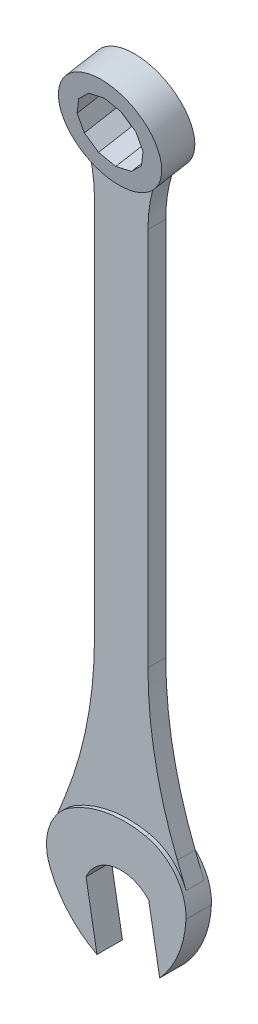
SolidWorks part; units mm, degrees
ref_plane "Front Plane" through (0, 0, 0) normal (1, 0, 0) x (0, 1, 0)
ref_plane "Top Plane" through (0, 0, 0) normal (0, 0, 1) x (0, 1, 0)
ref_plane "Right Plane" through (0, 0, 0) normal (0, 1, 0) x (-1, 0, 0)
sketch "head + handle sketch" plane through (0, 0, 0) normal (0, 0, 1) x (0, 1, 0)
  line L0 (-1.3783, 7.8169) -> (-16.8371, 5.0911)
  line L1 (1.3783, -7.8169) -> (-14.0804, -10.5427)
  line L2 (-1.3783, 7.8169) -> (1.3783, -7.8169) construction
  line L3 (-5.0941, -0.8982) -> (0, 0) construction
  line L4 (-5.0941, -0.8982) -> (-10.0056, -1.7643) construction
  line L5 (0, 0) -> (-15.9394, 0) construction
  line L6 (-14.0804, -10.5427) -> (-16.8371, 5.0911) construction
  line L7 (-4.1052, 16.7007) -> (1.8543, -17.0976) construction
  line L8 (14.8371, -7.0558) -> (11.5291, 11.7048) construction
  line L9 (-14.3514, 15.2013) -> (9.6201, 19.4282) construction
  line L10 (-9.4772, -19.403) -> (13.9076, -15.2796) construction
  line L11 (50.3209, 6.6675) -> (145.1557, 6.6675)
  line L12 (164.2057, 12.065) -> (164.2057, -12.065)
  line L13 (0, 0) -> (164.2057, 0) construction
  line L14 (145.1557, -6.6675) -> (50.5079, -6.6675)
  line L15 (12.7689, 13.862) -> (5.4557, 16.771)
  line L16 (12.621, -13.9958) -> (7.1516, -16.194)
  line L17 (165.1, 0) -> (165.1, 14.0481)
  arc A0 (-1.3783, 7.8169) -> (1.3783, -7.8169) centre (-5.0941, -0.8982) cw
  arc A1 (-16.8371, 5.0911) -> (-4.1052, 16.7007) centre (5.6286, -6.7602) cw
  arc A2 (-4.1052, 16.7007) -> (11.5291, 11.7048) centre (0.7617, 4.9703) cw
  arc A3 (11.5291, 11.7048) -> (14.8371, -7.0558) centre (-10.0056, -1.7643) cw
  arc A4 (14.8371, -7.0558) -> (1.8543, -17.0976) centre (2.4157, -4.41) cw
  arc A5 (1.8543, -17.0976) -> (-14.0804, -10.5427) centre (2.9771, 8.2776) cw
  arc A6 (50.3209, 6.6675) -> (12.7689, 13.862) centre (50.3209, 108.2675) cw
  arc A7 (145.1557, 6.6675) -> (164.2057, 12.065) centre (145.1557, 42.9839) ccw
  arc A8 (145.1557, -6.6675) -> (164.2057, -12.065) centre (145.1557, -42.9839) cw
  arc A9 (50.5079, -6.6675) -> (12.621, -13.9958) centre (50.5079, -108.2675) ccw
  point P29 (30.8557, 6.6675)
  point P37 (165.1, 0)
  point P41 (30.8557, -6.6675)
  dimension "D2" = 9.4742
  dimension "D3" = 25.4
  dimension "D4" = 12.7
  dimension "D5" = 25.4
  dimension "D7" = 10
  dimension "D9" = 34.925
  dimension "D11" = 101.6
  dimension "D16" = 101.6
  dimension "D1" = 15.875
  dimension "D6" = 10.16
  dimension "D8" = 15.6972
  dimension "D10" = 25.4
  dimension "D12" = 19.05
  dimension "D13" = 24.13
  dimension "D14" = 6.6675
  dimension "D15" = 158.75
  dimension "D17" = 165.1
extrude "head extrude" add sketch "head + handle sketch" along normal blind 3.175 and the other way blind 3.175 contours A5 A4 A3 A2 A1 L0 A0 L1 region at (-6.921, -9.19, 0)
extrude "handle extrude" add sketch "Sketch2<3>" along normal blind 2.2225 and the other way blind 2.2225 contours L14 A8 L12 A7 L11 A2 A3 A4 region at (-0.0501, 86.1411, 0)
sketch "Sketch2<3>" plane through (0, 0, 0) normal (0, 0, 1) x (0, 1, 0) same geometry as "head + handle sketch"
ref_plane "rear circle plane" through (0, 4.9784, -28.2338) normal (0, 0.1736, -0.9848) x (-1, 0, 0)
sketch "rear circle sketch" plane through (0, 4.9784, -28.2338) normal (0, 0.1736, -0.9848) x (-1, 0, 0)
  line L0 (-7.1166, 158.483) -> (-4.1088, 155.4752)
  line L1 (7.1166, 166.7005) -> (4.1088, 169.7083)
  line L2 (4.1088, 169.7083) -> (0, 170.8093)
  line L3 (0, 170.8093) -> (-4.1088, 169.7083)
  line L4 (-4.1088, 169.7083) -> (-7.1166, 166.7005)
  line L5 (-7.1166, 166.7005) -> (-8.2175, 162.5918)
  line L6 (-8.2175, 162.5918) -> (-7.1166, 158.483)
  line L7 (-4.1088, 155.4752) -> (0, 154.3743)
  line L8 (0, 154.3743) -> (4.1088, 155.4752)
  line L9 (4.1088, 155.4752) -> (7.1166, 158.483)
  line L10 (7.1166, 158.483) -> (8.2175, 162.5918)
  line L11 (8.2175, 162.5918) -> (7.1166, 166.7005)
  line L12 (0, 0) -> (0, 161.7111) construction
  circle A0 centre (0, 162.5918) radius 12.7
  circle A1 centre (0, 162.5918) radius 7.9375 construction
  point P3 (0, 0)
  point P19 (4.7816, 170.8738)
  dimension "D1" = 25.4
  dimension "D2" = 15.875
extrude "rear circle" add sketch "rear circle sketch" against normal blind 5.08 and the other way blind 3.302 contours L10 L11 L1 L2 L3 L4 L5 L6 L0 L7 L8 L9 | A0 L11 L10 L9 L8 L7 L0 L6 L5 L4 L3 L2 L1 region at (0, 165.1, 0) region at (12.3408, 165.1, 0)
extrude "cut rear hole" cut sketch "rear circle sketch<3>" against normal through all both and the other way through all contours L10 L11 L1 L2 L3 L4 L5 L6 L0 L7 L8 L9 region at (0, 165.1, 0)
sketch "rear circle sketch<3>" plane through (0, 4.9784, -28.2338) normal (0, 0.1736, -0.9848) x (-1, 0, 0) same geometry as "rear circle sketch"
